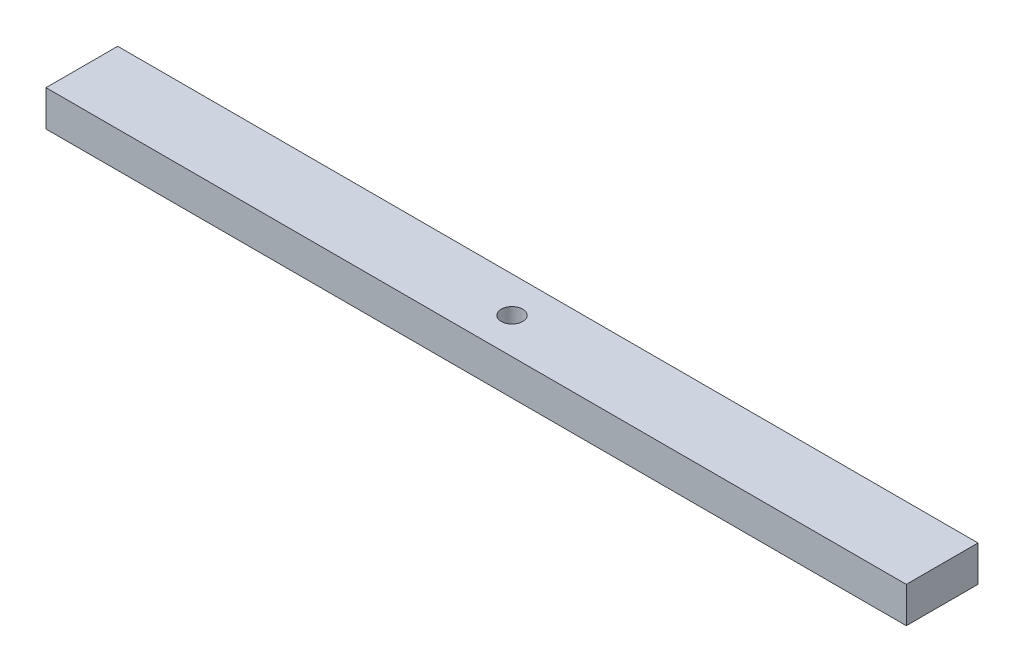
SolidWorks part; units mm, degrees
ref_plane "Front Plane" through (0, 0, 0) normal (0, 0, 1) x (1, 0, 0)
ref_plane "Top Plane" through (0, 0, 0) normal (0, 1, 0) x (1, 0, 0)
ref_plane "Right Plane" through (0, 0, 0) normal (1, 0, 0) x (0, 0, -1)
sketch "Sketch2" plane through (0, 0, 0) normal (0, 1, 0) x (1, 0, 0)
  line L1 (-76.2, -6.35) -> (76.2, -6.35)
  line L2 (-76.2, -6.35) -> (-76.2, 6.35)
  line L3 (-76.2, 6.35) -> (76.2, 6.35)
  line L4 (76.2, -6.35) -> (76.2, 6.35)
  line L5 (-76.2, -6.35) -> (76.2, 6.35) construction
  line L6 (-76.2, 6.35) -> (76.2, -6.35) construction
  point P0 (0, 0)
  dimension "D1" = 152.4
  dimension "D2" = 12.7
extrude "Boss-Extrude1" add sketch "Sketch2" along normal blind 6.35
sketch "Sketch3" plane through (0, 0, 0) normal (0, -1, 0) x (1, 0, 0)
  circle A0 centre (0, 0) radius 1.8986
  dimension "D1" = 3.7973
extrude "Cut-Extrude1" cut sketch "Sketch3" against normal through all
